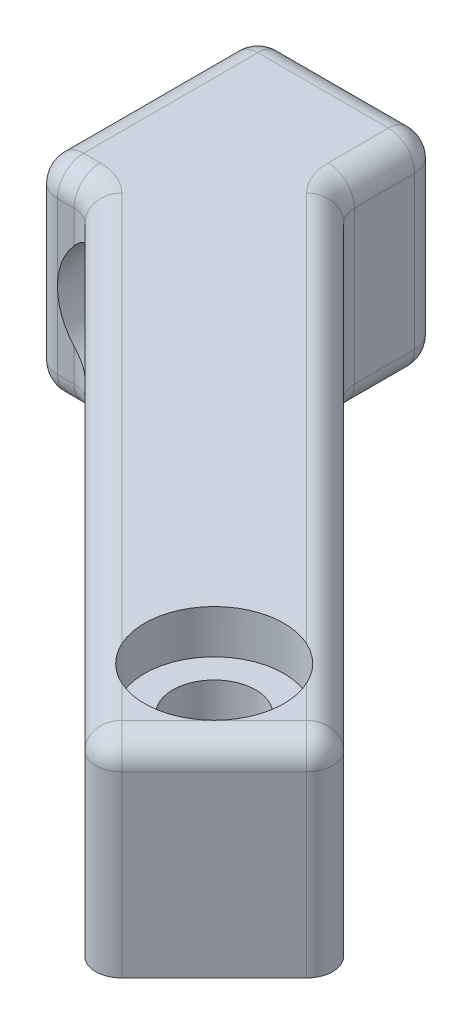
SolidWorks part; units mm, degrees
ref_plane "Front Plane" through (0, 0, 0) normal (0, 0, 1) x (1, 0, 0)
ref_plane "Top Plane" through (0, 0, 0) normal (0, 1, 0) x (1, 0, 0)
ref_plane "Right Plane" through (0, 0, 0) normal (1, 0, 0) x (0, 0, -1)
sketch "Sketch3" plane through (0, 0, 0) normal (0, 1, 0) x (1, 0, 0)
  line L1 (-59.9975, 62.4975) -> (-38.9975, 62.4975)
  line L2 (-59.9975, 62.4975) -> (-59.9975, 36.4975)
  line L3 (-59.9975, 36.4975) -> (-53.8467, 36.4975)
  line L4 (-38.9975, 62.4975) -> (-38.9975, 51.3467)
  line L5 (-59.9975, 62.4975) -> (-38.9975, 36.4975) construction
  line L6 (-59.9975, 36.4975) -> (-38.9975, 62.4975) construction
  line L8 (36.4975, -59.9975) -> (62.4975, -59.9975)
  line L9 (36.4975, -59.9975) -> (36.4975, -53.8467)
  line L10 (51.3467, -38.9975) -> (62.4975, -38.9975)
  line L11 (62.4975, -59.9975) -> (62.4975, -38.9975)
  line L12 (36.4975, -59.9975) -> (62.4975, -38.9975) construction
  line L13 (36.4975, -38.9975) -> (62.4975, -59.9975) construction
  line L14 (-49.4975, 49.4975) -> (49.4975, -49.4975) construction
  line L15 (-98.384, 0) -> (127.6464, 0) construction
  line L16 (-38.9975, 51.3467) -> (51.3467, -38.9975)
  line L18 (36.4975, -53.8467) -> (-53.8467, 36.4975)
  line L19 (36.4975, -38.9975) -> (62.4975, -38.9975) construction
  point P0 (-49.4975, 49.4975)
  point P5 (49.4975, -49.4975)
  point P12 (0, 0)
  dimension "D1" = 140
  dimension "D2" = 26
  dimension "D3" = 26
  dimension "D4" = 21
  dimension "D5" = 21
  dimension "D6" = 45
  dimension "D7" = 21
extrude "Boss-Extrude1" add sketch "Sketch3" along normal blind 37
sketch "Sketch5" plane through (7.8063, 0, -4.5429) normal (-0.7071, 0, 0.7071) x (0.7071, 0, 0.7071)
  line L4 (61.5754, 18.5) -> (-66.1906, 18.5) construction
  line L5 (61.5754, 37) -> (61.5754, 0) construction
  line L6 (61.5754, 37) -> (-66.1906, 37) construction
  line L7 (61.5754, 0) -> (-66.1906, 0) construction
  line L12 (-66.1906, 0) -> (-74.0754, 0) construction
  line L13 (-74.0754, 0) -> (-88.9246, 0) construction
  line L14 (-88.9246, 37) -> (-88.9246, 0) construction
  line L15 (-66.1906, 37) -> (-66.1906, 0) construction
  line L17 (69.4602, 37) -> (61.5754, 37) construction
  line L18 (84.3094, 37) -> (69.4602, 37) construction
  line L19 (84.3094, 37) -> (84.3094, 0) construction
  line L22 (61.5754, 37) -> (12.1924, 37)
  line L23 (-9.8076, 0) -> (-66.1906, 0)
  line L24 (-66.1906, 0) -> (-74.0754, 0)
  line L25 (-74.0754, 0) -> (-88.9246, 0)
  line L26 (-88.9246, 13.5) -> (-88.9246, 0)
  line L29 (69.4602, 37) -> (61.5754, 37)
  line L30 (84.3094, 37) -> (69.4602, 37)
  line L31 (84.3094, 37) -> (84.3094, 23.5)
  line L32 (84.3094, 23.5) -> (12.1924, 23.5)
  line L33 (12.1924, 23.5) -> (12.1924, 37)
  line L34 (-88.9246, 13.5) -> (-9.8076, 13.5)
  line L35 (-9.8076, 13.5) -> (-9.8076, 0)
  line L36 (1.1924, 0) -> (1.1924, 71.3842) construction
  dimension "D1" = 11
  dimension "D2" = 11
  dimension "D3" = 10
  dimension "D4" = 5
extrude "Cut-Extrude1" cut sketch "Sketch5" against normal through all both and the other way through all
sketch "Sketch6" plane through (62.4975, 0, 0) normal (1, 0, 0) x (0, 0, -1)
  line L0 (-49.4975, 11.75) -> (-49.4975, 0) construction
  line L1 (-59.9975, 0) -> (-38.9975, 0) construction
  line L2 (-49.4975, 11.75) -> (-59.9975, 11.75) construction
  line L3 (-59.9975, 23.5) -> (-59.9975, 0) construction
  circle A0 centre (-49.4975, 11.75) radius 7.5
  dimension "D1" = 15
extrude "Cut-Extrude2" cut sketch "Sketch6" against normal through all
sketch "Sketch7" plane through (0, 0, -62.4975) normal (0, 0, -1) x (-1, 0, 0)
  line L0 (49.4975, 25.25) -> (49.4975, 13.5) construction
  line L1 (38.9975, 13.5) -> (59.9975, 13.5) construction
  line L2 (49.4975, 25.25) -> (59.9975, 25.25) construction
  line L3 (59.9975, 37) -> (59.9975, 13.5) construction
  circle A0 centre (49.4975, 25.25) radius 7.5
  dimension "D1" = 15
extrude "Cut-Extrude3" cut sketch "Sketch7" against normal through all
fillet "Fillet1" radius 3 38 edges at (56.9221, 0, 38.9975) (56.9221, 23.5, 38.9975) (-38.9975, 25.25, -51.3467) (26.109, 0, 13.7598) (51.3467, 11.75, 38.9975) (33.8872, 23.5, 21.538) (62.4975, 0, 49.4975) (62.4975, 11.75, 59.9975) (62.4975, 23.5, 49.4975) (62.4975, 11.75, 38.9975) (-6.5533, 0, -4.0533) (-33.9123, 13.5, -16.5631) (-19.0631, 13.5, -31.4123) (-38.9975, 13.5, -56.9221) (-56.9221, 13.5, -36.4975) (-59.9975, 25.25, -36.4975) (-59.9975, 13.5, -49.4975) (-59.9975, 25.25, -62.4975) (-49.4975, 13.5, -62.4975) (-38.9975, 25.25, -62.4975) (-26.1341, 37, -8.7849) (-56.9221, 37, -36.4975) (-59.9975, 37, -49.4975) (-49.4975, 37, -62.4975) (-38.9975, 37, -56.9221) (-11.2849, 37, -23.6341) (9.003, 37, 11.503) (19.038, 23.5, 36.3872) (11.2598, 0, 28.609) (49.4975, 0, 59.9975) (49.4975, 23.5, 59.9975) (36.4975, 11.75, 59.9975) (36.4975, 0, 56.9221) (-53.8467, 16.3199, -36.4975) (-53.8467, 34.1801, -36.4975) (36.4975, 20.6801, 53.8467) (36.4975, 2.8199, 53.8467) (36.4975, 23.5, 56.9221)
sketch "Sketch8" plane through (0, 13.5, 0) normal (0, -1, 0) x (1, 0, 0)
  line L1 (73.0366, 82.0237) -> (-73.0366, 82.0237)
  line L2 (73.0366, 82.0237) -> (73.0366, -82.0237)
  line L3 (73.0366, -82.0237) -> (-73.0366, -82.0237)
  line L4 (-73.0366, 82.0237) -> (-73.0366, -82.0237)
  line L5 (73.0366, 82.0237) -> (-73.0366, -82.0237) construction
  line L6 (73.0366, -82.0237) -> (-73.0366, 82.0237) construction
  point P0 (0, 0)
extrude "Cut-Extrude4" cut sketch "Sketch8" along normal through all
sketch "Sketch9" plane through (10.253, 0, 10.253) normal (0.7071, 0, 0.7071) x (0.7071, 0, -0.7071)
  line L1 (-55.551, -63.2638) -> (55.551, -63.2638)
  line L2 (-55.551, -63.2638) -> (-55.551, 63.2638)
  line L3 (-55.551, 63.2638) -> (55.551, 63.2638)
  line L4 (55.551, -63.2638) -> (55.551, 63.2638)
  line L5 (-55.551, -63.2638) -> (55.551, 63.2638) construction
  line L6 (-55.551, 63.2638) -> (55.551, -63.2638) construction
  point P0 (0, 0)
extrude "Cut-Extrude5" cut sketch "Sketch9" along normal through all
sketch "Sketch10" plane through (0, 37, 0) normal (0, -1, 0) x (1, 0, 0)
  line L0 (1.2249, 3.7249) -> (-6.1997, 11.1495) construction
  line L1 (-13.9779, 3.3713) -> (1.5784, 18.9277) construction
  line L2 (1.2249, 3.7249) -> (9.003, 11.503) construction
  line L3 (16.4277, 4.0784) -> (1.5784, 18.9277) construction
  line L4 (16.4277, 4.0784) -> (0.8713, -11.4779) construction
  circle A0 centre (1.2249, 3.7249) radius 8
  dimension "D1" = 16
extrude "Cut-Extrude6" cut sketch "Sketch10" along normal blind 5 contours A0
sketch "Sketch11" plane through (0, 37, 0) normal (0, 1, 0) x (1, 0, 0)
  circle A0 centre (1.2249, -3.7249) radius 8 construction
  circle A2 centre (1.2249, -3.7249) radius 4.75
  dimension "D1" = 9.5
extrude "Cut-Extrude7" cut sketch "Sketch11" against normal through all
sketch "Sketch12" plane through (0, 13.5, 0) normal (0, -1, 0) x (1, 0, 0)
  circle A0 centre (1.2249, 3.7249) radius 8
  dimension "D1" = 16
extrude "Cut-Extrude8" cut sketch "Sketch12" against normal blind 6
fillet "Fillet2" radius 3 6 edges at (1.5784, 36.1213, 17.685) (15.185, 36.1213, 4.0784) (0.8713, 15, -11.4779) (-13.9779, 15, 3.3713) (1.5784, 23.75, 18.9277) (16.4277, 23.75, 4.0784)
equation "\"D2@Sketch3\"=\"D3@Sketch3\""
equation "\"D5@Sketch3\"=\"D4@Sketch3\""
equation "\"D1@Sketch5\"=\"D2@Sketch5\""
equation "\"D4@Sketch5\"=\"D3@Sketch5\"/2"
